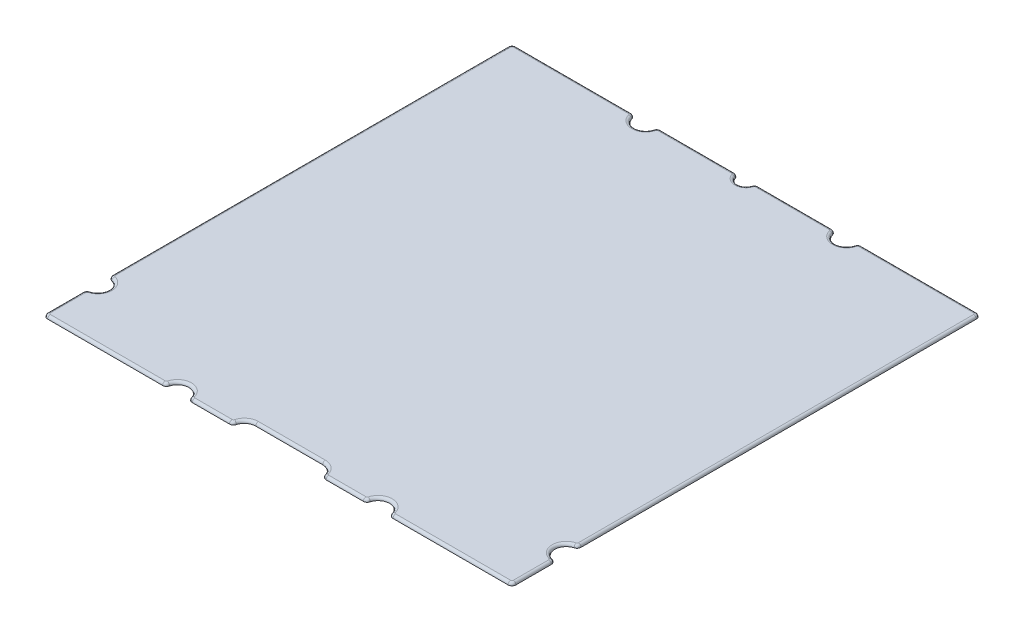
SolidWorks part; units mm, degrees
ref_plane "Front Plane" through (0, 0, 0) normal (0, 0, 1) x (1, 0, 0)
ref_plane "Top Plane" through (0, 0, 0) normal (0, 1, 0) x (1, 0, 0)
ref_plane "Right Plane" through (0, 0, 0) normal (1, 0, 0) x (0, 0, -1)
sketch "Sketch1" plane through (0, 0, 0) normal (0, 1, 0) x (1, 0, 0)
  line L0 (-25, -166.5) -> (25, -166.5)
  line L1 (-175, 175) -> (-83.5, 175)
  line L2 (-175, 175) -> (-175, -126)
  line L3 (-175, -175) -> (-83.5, -175)
  line L4 (175, 175) -> (175, -126)
  line L5 (-175, 175) -> (175, -175) construction
  line L6 (-175, -175) -> (175, 175) construction
  line L7 (33.5, -175) -> (66.5, -175)
  line L8 (-75, -175) -> (75, -175) construction
  line L9 (-66.5, -175) -> (-33.5, -175)
  line L10 (83.5, -175) -> (175, -175)
  line L11 (175, -143) -> (175, -175)
  line L12 (-175, -143) -> (-175, -175)
  line L13 (-66.5, 175) -> (-6.5, 175)
  line L14 (6.5, 175) -> (66.5, 175)
  line L15 (83.5, 175) -> (175, 175)
  line L17 (-25, -175) -> (25, -175) construction
  line L18 (-177.5, 177.5) -> (177.5, 177.5) construction
  line L19 (-177.5, 177.5) -> (-177.5, -177.5) construction
  line L20 (-177.5, -177.5) -> (177.5, -177.5) construction
  line L21 (177.5, 177.5) -> (177.5, -177.5) construction
  line L22 (-177.5, 177.5) -> (177.5, -177.5) construction
  line L23 (-177.5, -177.5) -> (177.5, 177.5) construction
  arc A0 (-6.5, 175) -> (6.5, 175) centre (0, 175) ccw
  arc A1 (66.5, 175) -> (83.5, 175) centre (75, 175) ccw
  arc A2 (-83.5, 175) -> (-66.5, 175) centre (-75, 175) ccw
  arc A3 (-66.5, -175) -> (-83.5, -175) centre (-75, -175) ccw
  arc A4 (-25, -166.5) -> (-33.5, -175) centre (-25, -175) ccw
  arc A5 (33.5, -175) -> (25, -166.5) centre (25, -175) ccw
  arc A6 (83.5, -175) -> (66.5, -175) centre (75, -175) ccw
  arc A7 (-175, -143) -> (-175, -126) centre (-175, -134.5) ccw
  arc A8 (175, -126) -> (175, -143) centre (175, -134.5) ccw
  point P0 (0, 0)
  point P15 (0, -175)
  point P26 (0, 170.5)
  point P27 (0, -166.5)
  point P38 (0, 0)
  dimension "D3" = 8.5
  dimension "D8" = 6.5
  dimension "D1" = 350
  dimension "D2" = 50
  dimension "D5" = 305
  dimension "D6" = 350
  dimension "D9" = 150
  dimension "D10" = 7
  dimension "D11" = 355
extrude "Boss-Extrude1" add sketch "Sketch1" along normal blind 2
fillet "Fillet1" radius 3 20 edges at (175, 1, -175) (83.5, 1, -175) (66.5, 1, -175) (6.5, 1, -175) (-6.5, 1, -175) (-83.5, 1, -175) (-66.5, 1, -175) (-175, 1, -175) (-175, 1, 143) (-175, 1, 126) (-175, 1, 175) (-83.5, 1, 175) (-66.5, 1, 175) (-33.5, 1, 175) (33.5, 1, 175) (66.5, 1, 175) (83.5, 1, 175) (175, 1, 175) (175, 1, 143) (175, 1, 126)
fillet "Fillet2" radius 2 42 edges at (174.382, 2, 125.222) (166.5, 2, 134.5) (174.382, 2, 143.778) (175, 2, 158.8009) (174.1213, 2, 174.1213) (129.0509, 2, 175) (84.278, 2, 174.382) (75, 2, 166.5) (65.722, 2, 174.382) (50, 2, 175) (34.278, 2, 174.382) (30.1673, 2, 168.251) (0, 2, 166.5) (-30.1673, 2, 168.251) (-34.278, 2, 174.382) (-50, 2, 175) (-65.722, 2, 174.382) (-75, 2, 166.5) (-84.278, 2, 174.382) (-129.0509, 2, 175) (-174.1213, 2, 174.1213) (-175, 2, 158.8009) (-174.382, 2, 143.778) (-166.5, 2, 134.5) (-174.382, 2, 125.222) (-175, 2, -24.3009) (-174.1213, 2, -174.1213) (-129.0509, 2, -175) (-84.278, 2, -174.382) (-75, 2, -166.5) (-65.722, 2, -174.382) (-36.456, 2, -175) (-7.2592, 2, -174.4333) (0, 2, -168.5) (7.2592, 2, -174.4333) (36.456, 2, -175) (65.722, 2, -174.382) (75, 2, -166.5) (84.278, 2, -174.382) (129.0509, 2, -175) (174.1213, 2, -174.1213) (175, 2, -24.3009)
equation "\"heater_thickness\"= 2mm"
equation "\"D1@Boss-Extrude1\"=\"heater_thickness\""
equation "\"D1@Fillet2\"=\"heater_thickness\""
